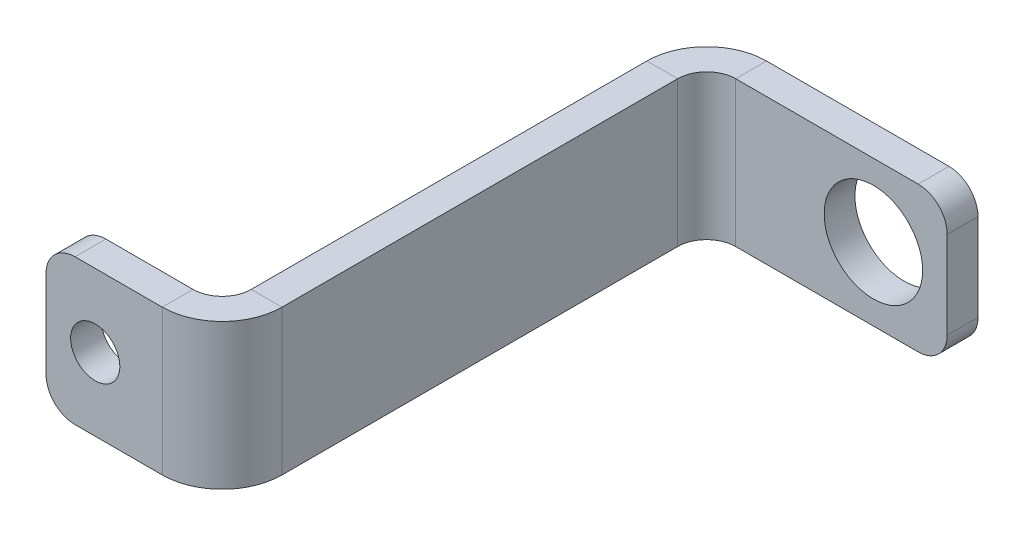
SolidWorks part; units mm, degrees
note: The reader was unsure of these and kept them because the rebuilt part matched: flange length of "Edge-Flange1", "Edge-Flange2".
material "Custom Plastic"
ref_plane "X-Y Datum" through (0, 0, 0) normal (0, 0, 1) x (1, 0, 0)
ref_plane "X-Z Datum" through (0, 0, 0) normal (0, 1, 0) x (1, 0, 0)
ref_plane "Y-Z Datum" through (0, 0, 0) normal (1, 0, 0) x (0, 0, -1)
sketch "Sketch1" plane through (0, 0, 0) normal (0, 0, 1) x (1, 0, 0)
  line L1 (-7.5, -7.5) -> (7.5, -7.5)
  line L2 (-7.5, -7.5) -> (-7.5, 7.5)
  line L3 (-7.5, 7.5) -> (7.5, 7.5)
  line L4 (7.5, -7.5) -> (7.5, 7.5)
  line L5 (-7.5, -7.5) -> (7.5, 7.5) construction
  line L6 (-7.5, 7.5) -> (7.5, -7.5) construction
  point P0 (0, 0)
  dimension "D1" = 15
  dimension "D2" = 15
base flange "Base-Flange2" sketch "Sketch1" thickness 3.175 reverse thickness direction no parameters "D1"=10
edge flange "Edge-Flange1" sketch "Sketch13" flange angle 90 flange length 50 flange position material outside bend radius 3 thickness 3.175 relief rectangular parameters "D6"=10
sketch "Sketch13" plane through (7.5, 0, -3.175) normal (-1, 0, 0) x (0, 1, 0)
  line L2 (-7.5, 0) -> (-7.5, 46.825)
  line L3 (-7.5, 46.825) -> (7.5, 46.825)
  line L4 (7.5, 46.825) -> (7.5, 0)
  line L5 (7.5, 0) -> (-7.5, 0) construction
  line L6 (7.5, 0) -> (-7.5, 0)
bend "EdgeBend1" bend radius 3 bend angle 90 parameters "D5"=1
edge flange "Edge-Flange2" sketch "Sketch16" flange angle 90 flange length 28 flange position material outside bend radius 3 thickness 3.175 relief rectangular parameters "D6"=10
sketch "Sketch16" plane through (10.675, 0, -50) normal (0, 0, 1) x (0, -1, 0)
  line L2 (-7.5, 0) -> (-7.5, 24.825)
  line L3 (-7.5, 24.825) -> (7.5, 24.825)
  line L4 (7.5, 24.825) -> (7.5, 0)
  line L5 (7.5, 0) -> (-7.5, 0) construction
  line L6 (7.5, 0) -> (-7.5, 0)
bend "EdgeBend2" bend radius 3 bend angle 90 parameters "D5"=2
sketch "Sketch18" plane through (0, 0, 0) normal (0, 0, 1) x (1, 0, 0)
  line L0 (-7.5, 0) -> (-2.42, 0)
  line L1 (-7.5, 7.5) -> (-7.5, -7.5) construction
  circle A0 centre (-2.42, 0) radius 2.54
  dimension "D1" = 5.08
  dimension "D2" = 5.08
sketch "Sketch19" plane through (0, 0, -50) normal (0, 0, 1) x (1, 0, 0)
  line L0 (35.5, 0) -> (27.88, 0)
  line L1 (35.5, -7.5) -> (35.5, 7.5) construction
  circle A0 centre (27.88, 0) radius 5.08
extrude "Cut-Extrude1" cut sketch "Sketch18" against normal through all contours A0 normal cut yes
extrude "Cut-Extrude2" cut sketch "Sketch19" against normal through all
fillet "Fillet1" radius 3 4 edges at (35.5, -7.5, -51.5875) (35.5, 7.5, -51.5875) (-7.5, -7.5, -1.5875) (-7.5, 7.5, -1.5875)
sketch "Bend-Lines3" [suppressed] plane through (0, 0, 0) normal (0, 1, 0) x (1, 0, 0)
sketch "Bounding-Box3" [suppressed] plane through (0, 0, 0) normal (0, 1, 0) x (1, 0, 0)
sheet metal parameters "Sheet-Metal2" thickness 3.175 parameters "D1"=10
flat pattern "Flat-Pattern2" [suppressed]
sketch "Bend-Lines4" plane through (0, 0, 0) normal (0, 1, 0) x (1, 0, 0)
sketch3d "Bounding-Box4" [suppressed]
  line L0 (-15, -7.5, 0) -> (15, -7.5, 0) construction
  line L1 (-15, 7.5, 0) -> (15, 7.5, 0) construction
  line L2 (-15, -7.5, 0) -> (-15, 7.5, 0) construction
  line L3 (15, -7.5, 0) -> (15, 7.5, 0) construction
sheet metal parameters "Sheet-Metal3" thickness 3.175 parameters "D1"=10
flat pattern "Flat-Pattern2"
sketch "Bend-Lines4" plane through (0, 0, 0) normal (0, 0, 1) x (1, 0, 0)
  line L0 (15.603, -7.5) -> (15.603, 7.5) construction
  line L1 (15.603, -7.5) -> (15.603, 7.5) construction
sketch3d "Bounding-Box4" [suppressed]
  line L0 (-15, -7.5, 0) -> (23.031, -7.5, 0) construction
  line L1 (-15, 7.5, 0) -> (23.031, 7.5, 0) construction
  line L2 (-15, -7.5, 0) -> (-15, 7.5, 0) construction
  line L3 (23.031, -7.5, 0) -> (23.031, 7.5, 0) construction
bend of the flat pattern "Flatten-<EdgeBend1>1"
sheet metal parameters "Sheet-Metal4" thickness 3.175 parameters "D1"=10
flat pattern "Flat-Pattern2" [suppressed]
sketch "Bend-Lines4" plane through (0, 0, 0) normal (0, 0, 1) x (1, 0, 0)
  line L0 (8.103, -7.5) -> (8.103, 7.5) construction
  line L1 (8.103, -7.5) -> (8.103, 7.5) construction
  line L2 (61.134, -7.5) -> (61.134, 7.5) construction
  line L3 (61.134, -7.5) -> (61.134, 7.5) construction
sketch3d "Bounding-Box4" [suppressed]
  line L0 (-7.5, -7.5, 0) -> (86.5621, -7.5, 0) construction
  line L1 (-7.5, 7.5, 0) -> (86.5621, 7.5, 0) construction
  line L2 (-7.5, -7.5, 0) -> (-7.5, 7.5, 0) construction
  line L3 (86.5621, -7.5, 0) -> (86.5621, 7.5, 0) construction
bend of the flat pattern "Flatten-<EdgeBend1>1"
bend of the flat pattern "Flatten-<EdgeBend2>1"
sketch "Sketch19-1" plane through (51.0621, 0, 0) normal (0, 0, 1) x (1, 0, 0)
  line L0 (35.5, 0) -> (24.88, 0)
  circle A0 centre (24.88, 0) radius 5.08
sheet metal parameters "Sheet-Metal5" thickness 3.175 parameters "D1"=10
flat pattern "Flat-Pattern2" [suppressed]
sketch "Bend-Lines4" plane through (0, 0, 0) normal (0, 0, 1) x (1, 0, 0)
  line L0 (8.103, -7.5) -> (8.103, 7.5) construction
  line L1 (8.103, -7.5) -> (8.103, 7.5) construction
  line L2 (16.134, -7.5) -> (16.134, 7.5) construction
  line L3 (16.134, -7.5) -> (16.134, 7.5) construction
sketch3d "Bounding-Box4" [suppressed]
  line L0 (-7.5, -7.5, 0) -> (38.5621, -7.5, 0) construction
  line L1 (-7.5, 7.5, 0) -> (38.5621, 7.5, 0) construction
  line L2 (-7.5, -7.5, 0) -> (-7.5, 7.5, 0) construction
  line L3 (38.5621, -7.5, 0) -> (38.5621, 7.5, 0) construction
bend of the flat pattern "Flatten-<EdgeBend1>1"
bend of the flat pattern "Flatten-<EdgeBend2>1"
sketch "Sketch19-1" [suppressed] plane through (6.0621, 0, 0) normal (0, 0, 1) x (1, 0, 0)
  line L0 (32.5, 0) -> (27.38, 0)
  circle A0 centre (27.38, 0) radius 5.08
sheet metal parameters "Sheet-Metal6" thickness 3.175 parameters "D1"=10
flat pattern "Flat-Pattern2" [suppressed]
sketch "Bend-Lines4" plane through (0, 0, 0) normal (0, 0, 1) x (1, 0, 0)
  line L0 (8.103, -7.5) -> (8.103, 7.5) construction
  line L1 (8.103, -7.5) -> (8.103, 7.5) construction
  line L2 (56.134, -7.5) -> (56.134, 7.5) construction
  line L3 (56.134, -7.5) -> (56.134, 7.5) construction
sketch3d "Bounding-Box4" [suppressed]
  line L0 (-7.5, -7.5, 0) -> (81.5621, -7.5, 0) construction
  line L1 (-7.5, 7.5, 0) -> (81.5621, 7.5, 0) construction
  line L2 (-7.5, -7.5, 0) -> (-7.5, 7.5, 0) construction
  line L3 (81.5621, -7.5, 0) -> (81.5621, 7.5, 0) construction
bend of the flat pattern "Flatten-<EdgeBend1>1"
bend of the flat pattern "Flatten-<EdgeBend2>1"
sketch "Sketch19-1" [suppressed] plane through (46.0621, 0, 0) normal (0, 0, 1) x (1, 0, 0)
  line L0 (35.5, 0) -> (27.88, 0)
  circle A0 centre (27.88, 0) radius 5.08
